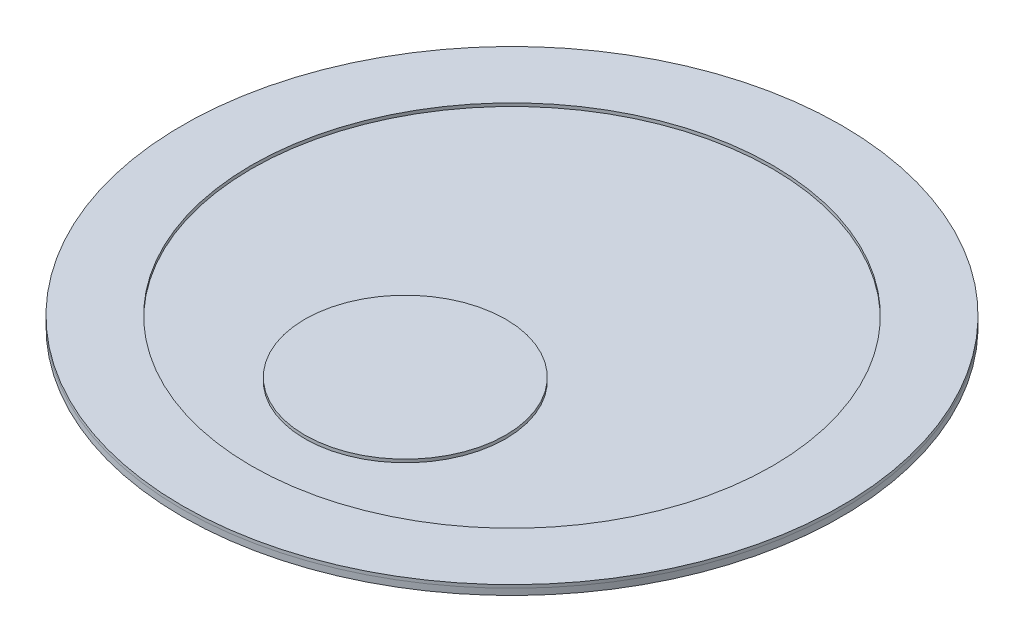
SolidWorks part; units mm, degrees
ref_plane "Front" through (0, 0, 0) normal (0, 0, 1) x (1, 0, 0)
ref_plane "Top" through (0, 0, 0) normal (0, 1, 0) x (1, 0, 0)
ref_plane "Right" through (0, 0, 0) normal (1, 0, 0) x (0, 0, -1)
sketch "Sketch1" plane through (0, 0, 0) normal (0, 1, 0) x (1, 0, 0)
  line L1 (0, 55.799) -> (0, -41.5) construction
  line L5 (0, -50) -> (0, -56.3751) construction
  circle A2 centre (0, 0) radius 41.5
  circle A3 centre (0, 0) radius 52.5
  circle A4 centre (0, -17) radius 16
  dimension "D1" = 105
  dimension "D3" = 83
  dimension "D2" = 32
  dimension "D4" = 17
extrude "Boss-Extrude1" add sketch "Sketch1" along normal blind 0.5 contours A3 A2 | A4 region at (-51.0151, 0, 0) region at (0, 0, 17)
fillet "Fillet1" [suppressed] radius 2
sketch "Sketch2" plane through (0, 0, 0) normal (0, -1, 0) x (1, 0, 0)
  circle A2 centre (0, 0) radius 52.5
  circle A3 centre (0, 0) radius 52.5 construction
extrude "Boss-Extrude2" add sketch "Sketch2" along normal blind 1
